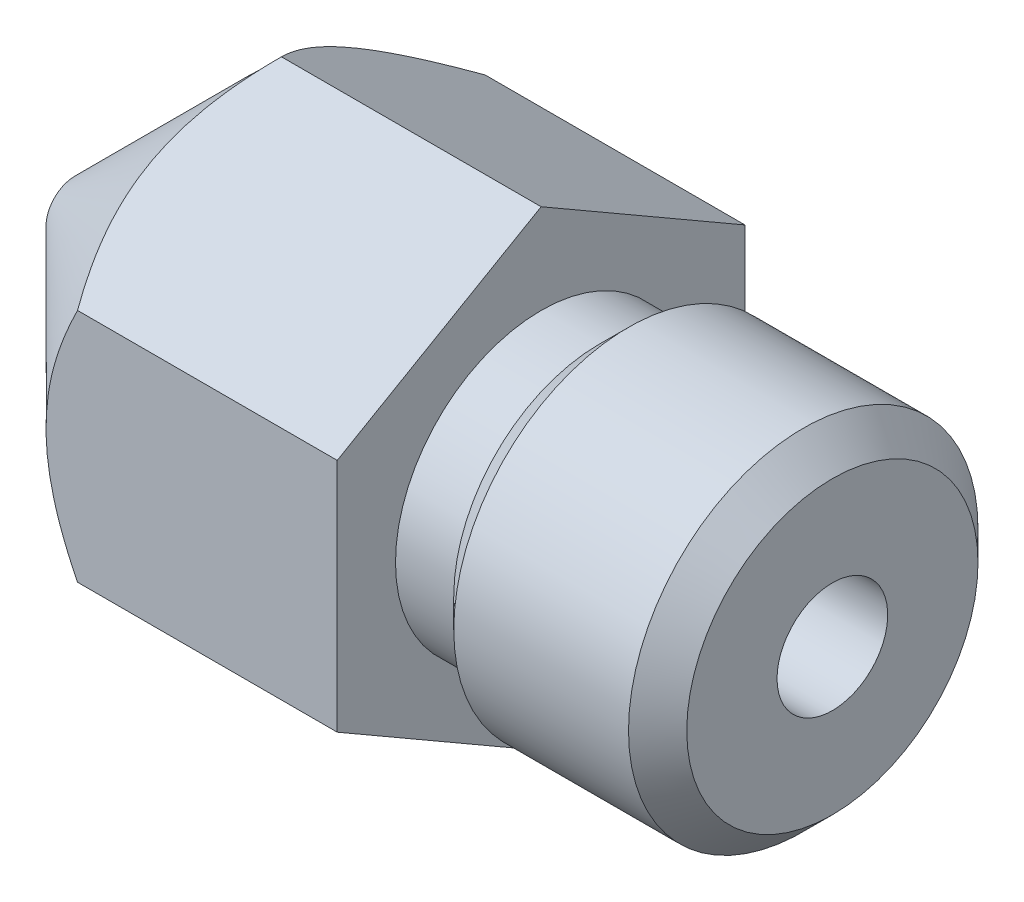
SolidWorks part; units mm, degrees
material "Cuivre"
ref_plane "Plan de face" through (0, 0, 0) normal (0, 0, 1) x (1, 0, 0)
ref_plane "Plan de dessus" through (0, 0, 0) normal (0, 1, 0) x (1, 0, 0)
ref_plane "Plan de droite" through (0, 0, 0) normal (1, 0, 0) x (0, 0, -1)
sketch "Esquisse1" plane through (0, 0, 0) normal (0, 0, 1) x (1, 0, 0)
  line L0 (1.25, 0.2) -> (2, 0.95)
  line L1 (2, 0.95) -> (13, 0.95)
  line L2 (13, 0.95) -> (13, 3)
  line L3 (13, 3) -> (9, 3)
  line L4 (9, 3) -> (9, 2.5)
  line L5 (9, 2.5) -> (8, 2.5)
  line L6 (8, 2.5) -> (8, 4.5)
  line L7 (8, 4.5) -> (4, 4.5)
  line L8 (4, 4.5) -> (0, 0.5)
  line L10 (0, 0.2) -> (1.25, 0.2)
  line L12 (0, 0.5) -> (0, 0.2)
  line L13 (0, 0) -> (13.8194, 0) construction
  dimension "D1" = 13
  dimension "D2" = 45
  dimension "D3" = 0.2
  dimension "D4" = 0.95
  dimension "D5" = 2.5
  dimension "D6" = 3
  dimension "D7" = 11
  dimension "D8" = 9
  dimension "D9" = 5
  dimension "D10" = 4
  dimension "D11" = 4.5
revolve "Révolution1" add sketch "Esquisse1" angle 360 about L13
cosmetic thread "Représentation de filetage1" parameters "D2"=4.891
sketch "Esquisse2" plane through (8, 0, 0) normal (1, 0, 0) x (0, 0, -1)
  line L1 (-3.5, -2.0207) -> (0, -4.0415)
  line L2 (0, -4.0415) -> (3.5, -2.0207)
  line L3 (3.5, -2.0207) -> (3.5, 2.0207)
  line L4 (3.5, 2.0207) -> (0, 4.0415)
  line L5 (0, 4.0415) -> (-3.5, 2.0207)
  line L6 (-3.5, 2.0207) -> (-3.5, -2.0207)
  circle A0 centre (0, 0) radius 3.5 construction
  dimension "D1" = 7
extrude "Enlèv. mat.-Extru.1" cut sketch "Esquisse2" against normal blind 10 flip side to cut
chamfer "Chanfrein1" distance 0.5 angle 45 2 edges at (13, 0, 3) (9, 0, 3)
